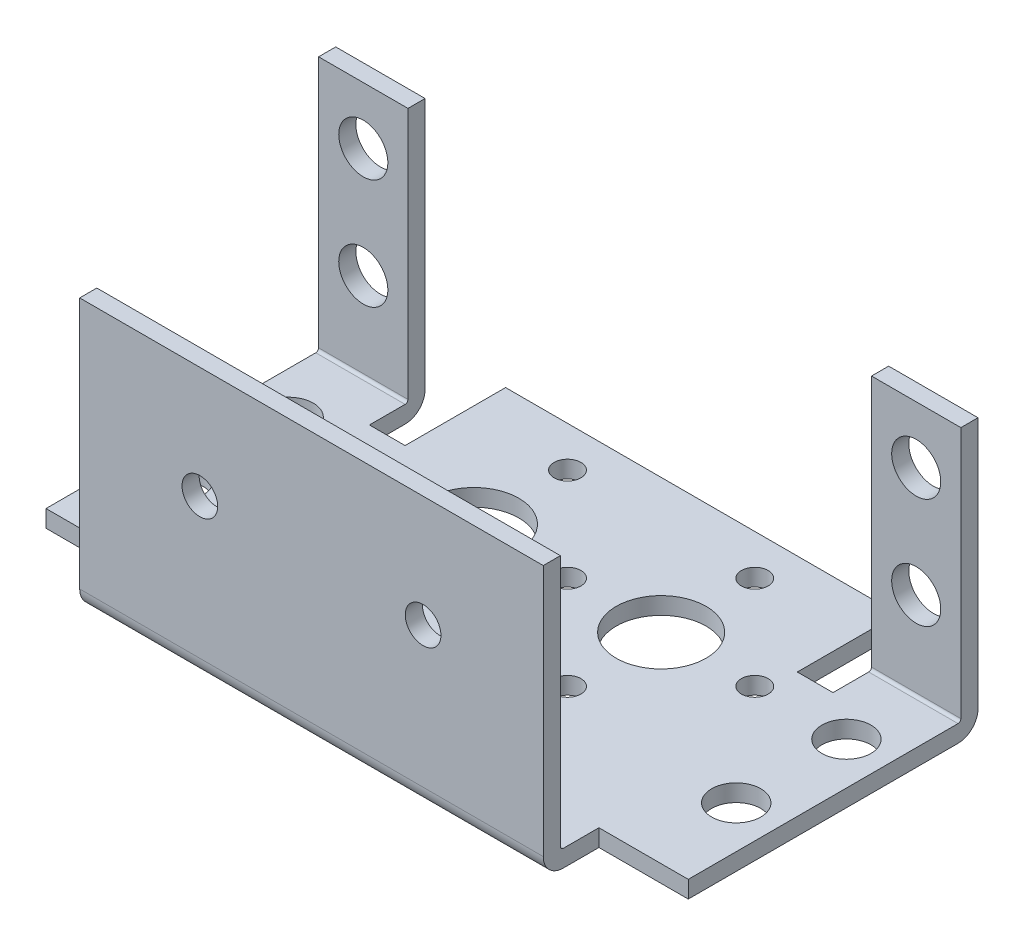
SolidWorks part; units mm, degrees
note: The reader was unsure of these and kept them because the rebuilt part matched: shared geometry of "Sketch3<3>".
ref_plane "Front" through (0, 0, 0) normal (0, 0, 1) x (1, 0, 0)
ref_plane "Top" through (0, 0, 0) normal (0, 1, 0) x (1, 0, 0)
ref_plane "Right" through (0, 0, 0) normal (1, 0, 0) x (0, 0, -1)
sketch "Sketch1" plane through (0, 0, 0) normal (0, 1, 0) x (1, 0, 0)
  line L0 (28.575, 0) -> (-28.575, 0)
  line L1 (-28.575, 0) -> (-28.575, -12.4079)
  line L3 (-20.6248, -17.3609) -> (-20.6248, -12.4079)
  line L4 (-20.6248, -12.4079) -> (-28.575, -12.4079)
  line L5 (-20.6248, -17.3609) -> (20.6248, -17.3609)
  line L6 (17.4498, 8.4201) -> (17.4498, 17.3609)
  line L7 (20.6248, 8.4201) -> (17.4498, 8.4201)
  line L8 (20.6248, 13.3731) -> (20.6248, 8.4201)
  line L9 (-28.575, 0) -> (-28.575, 13.3731)
  line L10 (-28.575, 13.3731) -> (-20.6248, 13.3731)
  line L11 (-20.6248, 13.3731) -> (-20.6248, 8.4201)
  line L12 (-20.6248, 8.4201) -> (-17.4498, 8.4201)
  line L13 (-17.4498, 8.4201) -> (-17.4498, 17.3609)
  line L14 (-17.4498, 17.3609) -> (17.4498, 17.3609)
  line L15 (28.575, 13.3731) -> (20.6248, 13.3731)
  line L16 (28.575, 0) -> (28.575, 13.3731)
  line L17 (20.6248, -12.4079) -> (28.575, -12.4079)
  line L18 (20.6248, -17.3609) -> (20.6248, -12.4079)
  line L19 (28.575, 0) -> (28.575, -12.4079)
  circle A0 centre (-24.8158, -4.3815) radius 2.1844
  circle A1 centre (-24.8158, 5.4229) radius 2.1844
  circle A2 centre (-8.3312, 5.4229) radius 4.0005
  circle A3 centre (8.3312, 13.7541) radius 1.1938
  circle A4 centre (-16.6624, 5.4229) radius 1.1938
  circle A5 centre (-8.3312, -2.9083) radius 1.1938
  circle A6 centre (-8.3312, 13.7541) radius 1.1938
  circle A7 centre (0, 5.4229) radius 1.1938
  circle A8 centre (8.3312, -2.9083) radius 1.1938
  circle A9 centre (16.6624, 5.4229) radius 1.1938
  circle A10 centre (8.3312, 5.4229) radius 4.0005
  circle A11 centre (24.8158, 5.4229) radius 2.1844
  circle A12 centre (24.8158, -4.3815) radius 2.1844
  point P40 (0, 17.3609)
extrude "Extrude1" add sketch "Sketch1" along normal blind 1.524
sketch "Sketch3" plane through (0, 0, 0) normal (0, 0, 1) x (1, 0, 0)
  line L0 (-28.575, 0) -> (-28.575, 24.2062)
  line L1 (-20.6248, 0) -> (-20.6248, 24.2062)
  line L2 (-20.6248, 24.2062) -> (-28.575, 24.2062)
  line L3 (20.6248, 24.2062) -> (28.575, 24.2062)
  line L6 (20.6248, 0) -> (20.6248, 24.2062)
  line L7 (-28.575, 0) -> (-20.6248, 0)
  line L8 (20.6248, 24.2062) -> (-20.6248, 24.2062)
  line L9 (28.575, 0) -> (28.575, 24.2062)
  line L10 (28.575, 0) -> (-20.6248, 0)
  circle A0 centre (-24.5999, 9.3218) radius 2.1844
  circle A1 centre (-24.5999, 19.1262) radius 2.1844
  circle A2 centre (-9.9314, 14.2748) radius 1.5875
  circle A3 centre (9.9314, 14.2748) radius 1.5875
  circle A4 centre (24.5999, 19.1262) radius 2.1844
  circle A5 centre (24.5999, 9.3218) radius 2.1844
extrude "Extrude3" add sketch "Sketch3" along normal blind 1.524 from vertex contours L0 L7 L1 L2 A1 A0 | L10 L9 L3 L6 A4 A5
extrude "Extrude4" add sketch "Sketch3<3>" against normal blind 1.524 from vertex contours L10 L6 L8 L1 A2 A3
sketch "Sketch3<3>" plane through (0, 0, 0) normal (0, 0, 1) x (1, 0, 0) same geometry as "Sketch3"
fillet "Fillet4" radius 1.778 3 edges at (0, 0, 17.3609) (-24.5999, 0, -13.3731) (24.5999, 0, -13.3731)
fillet "Fillet5" radius 0.254 3 edges at (0, 1.524, 15.8369) (24.5999, 1.524, -11.8491) (-24.5999, 1.524, -11.8491)
